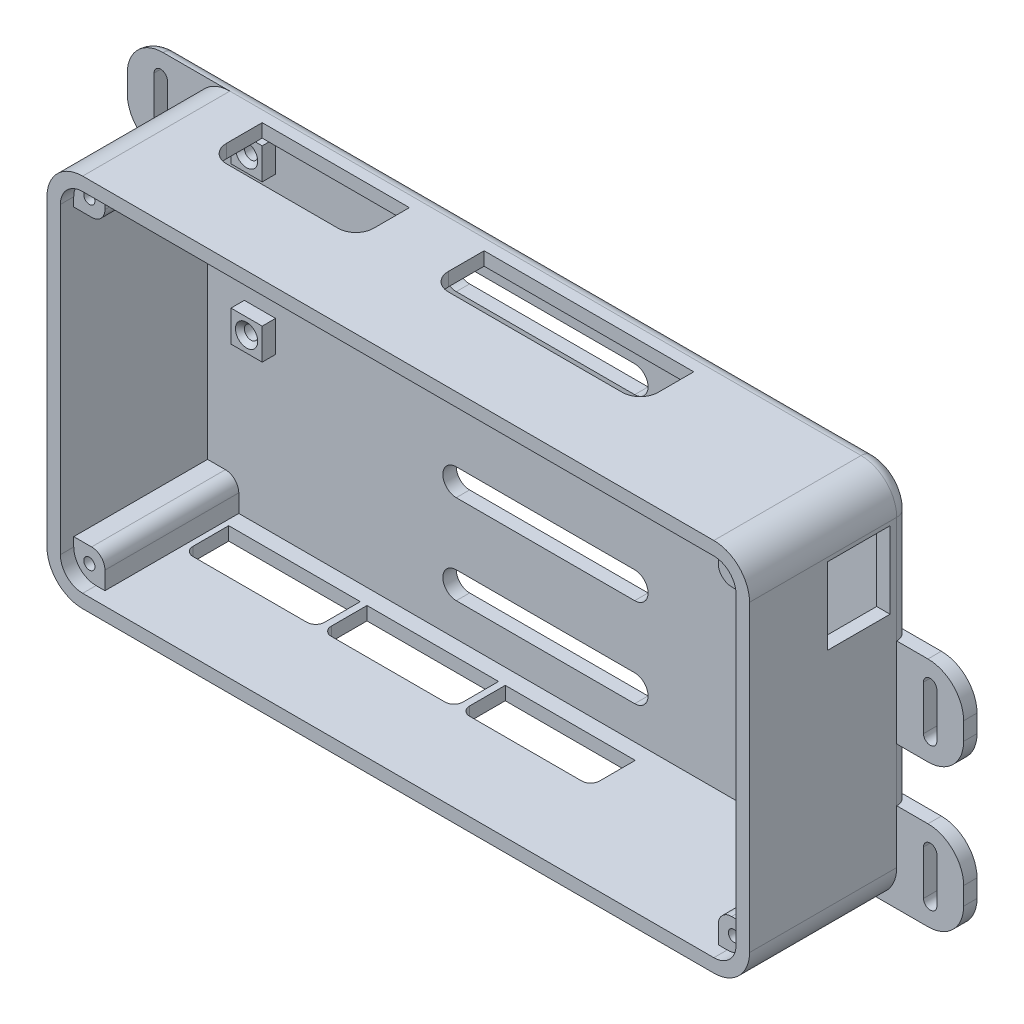
SolidWorks part; units mm, degrees
ref_plane "Piano frontale" through (0, 0, 0) normal (0, 0, 1) x (1, 0, 0)
ref_plane "Piano superiore" through (0, 0, 0) normal (0, 1, 0) x (1, 0, 0)
ref_plane "Piano destro" through (0, 0, 0) normal (1, 0, 0) x (0, 0, -1)
sketch "Schizzo2" plane through (0, 0, 0) normal (0, 0, 1) x (1, 0, 0)
  line L0 (-86.4596, 0) -> (99.8669, 0) construction
  line L1 (75.75, -39) -> (-75.75, -39)
  line L2 (75.75, -39) -> (75.75, 39)
  line L3 (75.75, 39) -> (-75.75, 39)
  line L4 (-75.75, -39) -> (-75.75, 39)
  line L5 (75.75, -39) -> (-75.75, 39) construction
  line L6 (75.75, 39) -> (-75.75, -39) construction
  line L7 (75.75, -39) -> (68.75, -39)
  line L8 (-75.75, 39) -> (-68.75, 39)
  line L9 (-75.75, 39) -> (-75.75, 32)
  line L10 (-75.75, 32) -> (-71.75, 32)
  line L11 (-68.75, 39) -> (-68.75, 35)
  line L12 (0, 67.9359) -> (0, -79.0704) construction
  line L13 (68.75, 39) -> (68.75, 35)
  line L14 (75.75, 32) -> (71.75, 32)
  line L15 (75.75, 39) -> (75.75, 32)
  line L16 (75.75, 39) -> (68.75, 39)
  line L17 (75.75, -39) -> (75.75, -32)
  line L18 (75.75, -32) -> (71.75, -32)
  line L19 (68.75, -39) -> (68.75, -35)
  line L20 (-68.75, -39) -> (-68.75, -35)
  line L21 (-75.75, -32) -> (-71.75, -32)
  line L22 (-75.75, -39) -> (-75.75, -32)
  line L23 (-75.75, -39) -> (-68.75, -39)
  line L24 (78.75, 42) -> (-78.75, 42)
  line L25 (-78.75, -39) -> (-78.75, 39)
  line L26 (78.75, -42) -> (-78.75, -42)
  line L27 (78.75, -39) -> (78.75, 39)
  line L28 (78.75, -39) -> (78.75, -42)
  line L29 (78.75, 39) -> (78.75, 42)
  line L30 (-78.75, -39) -> (-78.75, -42)
  line L31 (-78.75, 39) -> (-78.75, 42)
  line L32 (75.75, 42) -> (-75.75, 42) construction
  line L33 (75.75, -42) -> (-75.75, -42) construction
  line L34 (68.75, 39) -> (75.75, 32) construction
  circle A0 centre (72.25, 35.5) radius 1.25
  circle A1 centre (-72.25, 35.5) radius 1.25
  circle A2 centre (72.25, -35.5) radius 1.25
  circle A3 centre (-72.25, -35.5) radius 1.25
  arc A4 (68.75, 35) -> (71.75, 32) centre (71.75, 35) ccw
  arc A5 (71.75, -32) -> (68.75, -35) centre (71.75, -35) ccw
  arc A6 (-68.75, -35) -> (-71.75, -32) centre (-71.75, -35) ccw
  arc A7 (-68.75, 35) -> (-71.75, 32) centre (-71.75, 35) cw
  point P43 (68.75, 32)
  point P46 (68.75, -32)
  point P49 (-68.75, -32)
  point P52 (-68.75, 32)
  dimension "D9" = 2.5
  dimension "D10" = 3
  dimension "D1" = 78
  dimension "D2" = 151.5
  dimension "D3" = 7
  dimension "D4" = 7
  dimension "D5" = 3
  dimension "D6" = 3
  dimension "D7" = 3
  dimension "D8" = 3
extrude "Estrusione-Estrusione1" add sketch "Schizzo2" along normal blind 33 contours L31 L25 L30 L26 L28 L27 L29 L24 L1 L4 L3 L2 region at (76.965, 40.5, 0)
extrude "Estrusione-Estrusione2" add sketch "Schizzo2<3>" along normal blind 30 contours L11 L3 L4 L10 A1 | L14 L2 L3 L13 A0 | L19 L1 L2 L18 A2 | L21 L4 L1 L20 A3 region at (72.25, -38.901, 0) region at (-72.25, -38.901, 0) region at (73.75, 32.099, 0) region at (-75.651, 35.5, 0)
sketch "Schizzo2<3>" plane through (0, 0, 0) normal (0, 0, 1) x (1, 0, 0) same geometry as "Schizzo2"
sketch "Schizzo3" plane through (0, 42, 0) normal (0, 1, 0) x (1, 0, 0)
  line L0 (-103.3019, 0) -> (109.4618, 0) construction
  line L1 (-78.75, -33) -> (-78.75, 0) construction
  line L2 (-61, -2.5) -> (-61, -10.5)
  line L3 (78.75, -33) -> (78.75, 0) construction
  line L4 (-11.25, -2.5) -> (-11.25, -10.5)
  line L7 (-57, -14.5) -> (-32, -14.5)
  line L8 (-28, -2.5) -> (-28, -10.5)
  line L10 (-61, -2.5) -> (-28, -2.5)
  line L12 (-11.25, -2.5) -> (35.75, -2.5)
  line L17 (35.75, -2.5) -> (35.75, -10.5)
  line L18 (-7.25, -14.5) -> (31.75, -14.5)
  arc A4 (-57, -14.5) -> (-61, -10.5) centre (-57, -10.5) cw
  arc A5 (-32, -14.5) -> (-28, -10.5) centre (-32, -10.5) ccw
  arc A6 (31.75, -14.5) -> (35.75, -10.5) centre (31.75, -10.5) ccw
  arc A7 (-7.25, -14.5) -> (-11.25, -10.5) centre (-7.25, -10.5) cw
  point P3 (-103.3019, -3.5)
  point P4 (109.4618, -3.5)
  point P5 (-103.3019, -11.5)
  point P6 (109.4618, -11.5)
  dimension "D6" = 10.5
  dimension "D7" = 47
  dimension "D3" = 17.75
  dimension "D4" = 43
  dimension "D1" = 33
extrude "Taglio-Estrusione1" cut sketch "Schizzo3" against normal up to surface (3 mm away) up to face at (0, 39, 23.25)
sketch "Schizzo4" plane through (78.75, 0, 0) normal (1, 0, 0) x (0, 0, -1)
  line L0 (-1.5, 33.1164) -> (-15.5, 33.1164)
  line L1 (-15.5, 33.1164) -> (-15.5, 15.9327)
  line L4 (-1.5, 33.1164) -> (-1.5, 15.9327)
  line L5 (-1.5, 15.9327) -> (-15.5, 15.9327)
  point P0 (-3.5, 42)
  point P1 (-3.5, -5.2856)
  point P9 (-13.5, 42)
  point P10 (-13.5, -5.2856)
extrude "Taglio-Estrusione2" cut sketch "Schizzo4" against normal up to surface (10 mm away) up to face at (68.75, 37, 15)
sketch "Schizzo5" plane through (0, -42, 0) normal (0, -1, 0) x (1, 0, 0)
  line L1 (-67.5077, 3.5) -> (-67.5077, 11.5)
  line L4 (23.6305, 3.5) -> (23.6305, 11.5)
  line L5 (21.6305, 13.5) -> (11.9923, 13.5)
  line L6 (-55.5077, 13.5) -> (-65.5077, 13.5)
  line L11 (-38.0077, 3.5) -> (-38.0077, 11.5)
  line L12 (-36.5077, 3.5) -> (-36.5077, 11.5)
  line L15 (-7.0077, 3.5) -> (-7.0077, 11.5)
  line L16 (-5.5077, 3.5) -> (-5.5077, 11.5)
  line L17 (-67.5077, 3.5) -> (-38.0077, 3.5)
  line L18 (-36.5077, 3.5) -> (-21.0077, 3.5)
  line L19 (-40.0077, 13.5) -> (-50.0077, 13.5)
  line L20 (-19.0077, 13.5) -> (-34.5077, 13.5)
  line L21 (-21.0077, 3.5) -> (-7.0077, 3.5)
  line L22 (-5.5077, 3.5) -> (9.9923, 3.5)
  line L23 (-9.0077, 13.5) -> (-19.0077, 13.5)
  line L24 (9.9923, 3.5) -> (23.6305, 3.5)
  line L25 (11.9923, 13.5) -> (-3.5077, 13.5)
  line L38 (-55.5077, 13.5) -> (-50.0077, 13.5)
  arc A0 (21.6305, 13.5) -> (23.6305, 11.5) centre (21.6305, 11.5) cw
  arc A3 (-3.5077, 13.5) -> (-5.5077, 11.5) centre (-3.5077, 11.5) ccw
  arc A4 (-7.0077, 11.5) -> (-9.0077, 13.5) centre (-9.0077, 11.5) ccw
  arc A7 (-34.5077, 13.5) -> (-36.5077, 11.5) centre (-34.5077, 11.5) ccw
  arc A8 (-38.0077, 11.5) -> (-40.0077, 13.5) centre (-40.0077, 11.5) ccw
  arc A11 (-65.5077, 13.5) -> (-67.5077, 11.5) centre (-65.5077, 11.5) ccw
  point P33 (23.6305, 13.5)
sketch "Schizzo6" plane through (0, 0, 0) normal (0, 0, -1) x (-1, 0, 0)
  line L0 (67.5, 34.5) -> (108.7843, 34.5) construction
  line L2 (67.5, 38) -> (60.5, 38)
  line L3 (67.5, 38) -> (67.5, 31)
  line L4 (67.5, 31) -> (60.5, 31)
  line L5 (60.5, 38) -> (60.5, 31)
  line L6 (60.5, -4) -> (60.5, 3)
  line L7 (67.5, 3) -> (60.5, 3)
  line L8 (0, 0) -> (126.4431, 0) construction
  line L9 (67.5, -4) -> (67.5, 3)
  line L10 (67.5, -4) -> (60.5, -4)
  line L11 (60.5, 31) -> (67.5, 38) construction
  line L12 (60.5, -4) -> (67.5, 3) construction
  line L13 (0, 75.0983) -> (0, -97.4113) construction
  line L14 (-60.5, 31) -> (-67.5, 38) construction
  line L15 (-60.5, 38) -> (-60.5, 31)
  line L16 (-67.5, 31) -> (-60.5, 31)
  line L17 (-67.5, 38) -> (-67.5, 31)
  line L18 (-67.5, 38) -> (-60.5, 38)
  line L19 (0, 0) -> (-97.2233, 0) construction
  line L20 (-67.5, 38) -> (67.5, -38) construction
  line L21 (-60.5, -31) -> (-67.5, -38) construction
  line L22 (-67.5, -38) -> (-60.5, -38)
  line L23 (-67.5, -38) -> (-67.5, -31)
  line L24 (-67.5, -31) -> (-60.5, -31)
  line L25 (-60.5, -38) -> (-60.5, -31)
  circle A0 centre (64, 34.5) radius 1.5
  circle A1 centre (64, -0.5) radius 1.5
  circle A2 centre (-64, 34.5) radius 1.5
  circle A3 centre (-64, -34.5) radius 1.5
  dimension "D5" = 0.5
  dimension "D3" = 3
  dimension "D4" = 3
  dimension "D1" = 7
  dimension "D2" = 7
  dimension "D6" = 64
  dimension "D7" = 7
  dimension "D8" = 7
  dimension "D9" = 64
  dimension "D10" = 34.5
extrude "Estrusione-Estrusione3" add sketch "Schizzo6" against normal blind 3 separate body
chamfer "Smusso1" distance 1 angle 45 1 edges at (-65.5, 34.5, 3)
chamfer "Smusso2" distance 1 angle 45 1 edges at (-65.5, -0.5, 3)
chamfer "Smusso3" distance 1 angle 45 1 edges at (65.5, 34.5, 3)
chamfer "Smusso4" distance 1 angle 45 1 edges at (62.5, -34.5, 3)
extrude "Taglio-Estrusione3" cut sketch "Schizzo5" against normal up to surface (3 mm away) up to face at (0, -39, 23.25)
sketch "Schizzo7" plane through (0, 0, 0) normal (0, 0, -1) x (-1, 0, 0)
  line L1 (-78.75, 42) -> (78.75, 42)
  line L2 (-78.75, 42) -> (-78.75, -42)
  line L3 (-78.75, -42) -> (78.75, -42)
  line L4 (78.75, 42) -> (78.75, -42)
extrude "Estrusione-Estrusione4" add sketch "Schizzo7" along normal blind 3
sketch "Schizzo8" plane through (0, 0, -3) normal (0, 0, -1) x (-1, 0, 0)
  circle A0 centre (-64, 34.5) radius 1.5 construction
  circle A1 centre (64, 34.5) radius 1.5 construction
  circle A2 centre (64, -0.5) radius 1.5 construction
  circle A4 centre (-64, 34.5) radius 1.5
  circle A5 centre (64, 34.5) radius 1.5
  circle A6 centre (64, -0.5) radius 1.5
  circle A8 centre (-64, -34.5) radius 1.5 construction
  circle A9 centre (-64, -34.5) radius 1.5
extrude "Taglio-Estrusione4" cut sketch "Schizzo8" against normal blind 13
sketch "Schizzo9" plane through (0, 0, -3) normal (0, 0, -1) x (-1, 0, 0)
  line L0 (-110.5735, 0) -> (130.8262, 0) construction
  line L1 (0, 62.0649) -> (0, -64.0248) construction
  line L2 (-86.25, -22) -> (-86.25, -42) construction
  line L3 (-78.75, -42) -> (-93.75, -42)
  line L4 (-78.75, -42) -> (-78.75, -22)
  line L5 (-78.75, -22) -> (-93.75, -22)
  line L6 (-93.75, -42) -> (-93.75, -22)
  line L7 (-78.75, -27) -> (-93.75, -27) construction
  line L8 (-78.75, -37) -> (-93.75, -37) construction
  line L9 (-86.25, -37) -> (-86.25, -27) construction
  line L10 (-87.75, -37) -> (-87.75, -27)
  line L11 (-84.75, -37) -> (-84.75, -27)
  line L12 (78.75, -37) -> (93.75, -37) construction
  line L13 (78.75, -27) -> (93.75, -27) construction
  line L14 (86.25, -22) -> (86.25, -42) construction
  line L15 (93.75, -42) -> (93.75, -22)
  line L16 (78.75, -22) -> (93.75, -22)
  line L17 (78.75, -42) -> (78.75, -22)
  line L18 (78.75, -42) -> (93.75, -42)
  line L19 (86.25, -37) -> (86.25, -27) construction
  line L20 (87.75, -37) -> (87.75, -27)
  line L21 (84.75, -37) -> (84.75, -27)
  line L22 (86.25, 22) -> (86.25, 42) construction
  line L23 (78.75, 27) -> (93.75, 27) construction
  line L24 (78.75, 37) -> (93.75, 37) construction
  line L25 (78.75, 42) -> (93.75, 42)
  line L26 (78.75, 42) -> (78.75, 22)
  line L27 (78.75, 22) -> (93.75, 22)
  line L28 (93.75, 42) -> (93.75, 22)
  line L29 (86.25, 37) -> (86.25, 27) construction
  line L30 (87.75, 37) -> (87.75, 27)
  line L31 (84.75, 37) -> (84.75, 27)
  line L32 (-78.75, -10) -> (-93.75, -10)
  line L33 (-86.25, 10) -> (-86.25, -10) construction
  line L34 (-78.75, 10) -> (-93.75, 10)
  line L35 (-78.75, 5) -> (-93.75, 5) construction
  line L36 (-78.75, -10) -> (-78.75, 10)
  line L37 (-93.75, -10) -> (-93.75, 10)
  line L38 (-78.75, -5) -> (-93.75, -5) construction
  line L39 (-86.25, -5) -> (-86.25, 5) construction
  line L40 (-87.75, -5) -> (-87.75, 5)
  line L41 (-84.75, -5) -> (-84.75, 5)
  arc A0 (-87.75, -37) -> (-84.75, -37) centre (-86.25, -37) ccw
  arc A1 (-84.75, -27) -> (-87.75, -27) centre (-86.25, -27) ccw
  arc A2 (87.75, -37) -> (84.75, -37) centre (86.25, -37) cw
  arc A3 (84.75, -27) -> (87.75, -27) centre (86.25, -27) cw
  arc A4 (87.75, 37) -> (84.75, 37) centre (86.25, 37) ccw
  arc A5 (84.75, 27) -> (87.75, 27) centre (86.25, 27) ccw
  arc A6 (-87.75, -5) -> (-84.75, -5) centre (-86.25, -5) ccw
  arc A7 (-84.75, 5) -> (-87.75, 5) centre (-86.25, 5) ccw
  point P18 (-86.25, -32)
  point P35 (86.25, -32)
  point P52 (86.25, 32)
  point P69 (-86.25, 0)
  dimension "D5" = 15
  dimension "D1" = 15
  dimension "D2" = 20
  dimension "D6" = 20
  dimension "D3" = 5
  dimension "D4" = 5
extrude "Estrusione-Estrusione5" add sketch "Schizzo9" against normal blind 3
fillet "Raccordo2" radius 8 1 edges at (78.75, 42, 15)
fillet "Raccordo3" radius 5 1 edges at (75.75, 39, 31.5)
fillet "Raccordo4" radius 5 3 edges at (75.75, -39, 31.5) (-75.75, -39, 31.5) (-75.75, 39, 31.5)
fillet "Raccordo5" radius 8 3 edges at (-78.75, 42, 16.5)
fillet "Raccordo6" radius 8 8 edges at (93.75, 10, -1.5) (93.75, -10, -1.5) (93.75, -22, -1.5) (93.75, -42, -1.5) (-93.75, 42, -1.5) (-93.75, -22, -1.5) (-93.75, -42, -1.5) (-93.75, 22, -1.5)
fillet "Raccordo8" radius 3 7 edges at (-7.5, 42, -3) (-82.25, 22, -3) (-91.4069, 24.3431, -3) (-93.75, 32, -3) (-91.4069, 39.6569, -3) (76.4069, 39.6569, -3)
fillet "Raccordo9" radius 3 2 edges
sketch "Schizzo10" plane through (0, 0, 0) normal (0, 0, 1) x (1, 0, 0)
  line L0 (20, 31.4428) -> (-20, 31.4428) construction
  line L1 (20, 28.4428) -> (-20, 28.4428)
  line L2 (20, 34.4428) -> (-20, 34.4428)
  line L3 (0, 0) -> (0, 64.5922) construction
  line L4 (20, 11.4428) -> (-20, 11.4428) construction
  line L5 (20, 8.4428) -> (-20, 8.4428)
  line L6 (20, 14.4428) -> (-20, 14.4428)
  line L7 (20, -8.5572) -> (-20, -8.5572) construction
  line L8 (20, -11.5572) -> (-20, -11.5572)
  line L9 (20, -5.5572) -> (-20, -5.5572)
  line L10 (20, -28.5572) -> (-20, -28.5572) construction
  line L11 (20, -31.5572) -> (-20, -31.5572)
  line L12 (20, -25.5572) -> (-20, -25.5572)
  arc A0 (20, 28.4428) -> (20, 34.4428) centre (20, 31.4428) ccw
  arc A1 (-20, 34.4428) -> (-20, 28.4428) centre (-20, 31.4428) ccw
  arc A2 (20, 8.4428) -> (20, 14.4428) centre (20, 11.4428) ccw
  arc A3 (-20, 14.4428) -> (-20, 8.4428) centre (-20, 11.4428) ccw
  arc A4 (20, -11.5572) -> (20, -5.5572) centre (20, -8.5572) ccw
  arc A5 (-20, -5.5572) -> (-20, -11.5572) centre (-20, -8.5572) ccw
  arc A6 (20, -31.5572) -> (20, -25.5572) centre (20, -28.5572) ccw
  arc A7 (-20, -25.5572) -> (-20, -31.5572) centre (-20, -28.5572) ccw
  point P2 (0, 31.4428)
  point P14 (0, 11.4428)
  point P21 (0, -8.5572)
  point P28 (0, -28.5572)
  dimension "D1" = 6
  dimension "D2" = 40
  dimension "D3" = 4
extrude "Taglio-Estrusione5" cut sketch "Schizzo10" against normal blind 10
